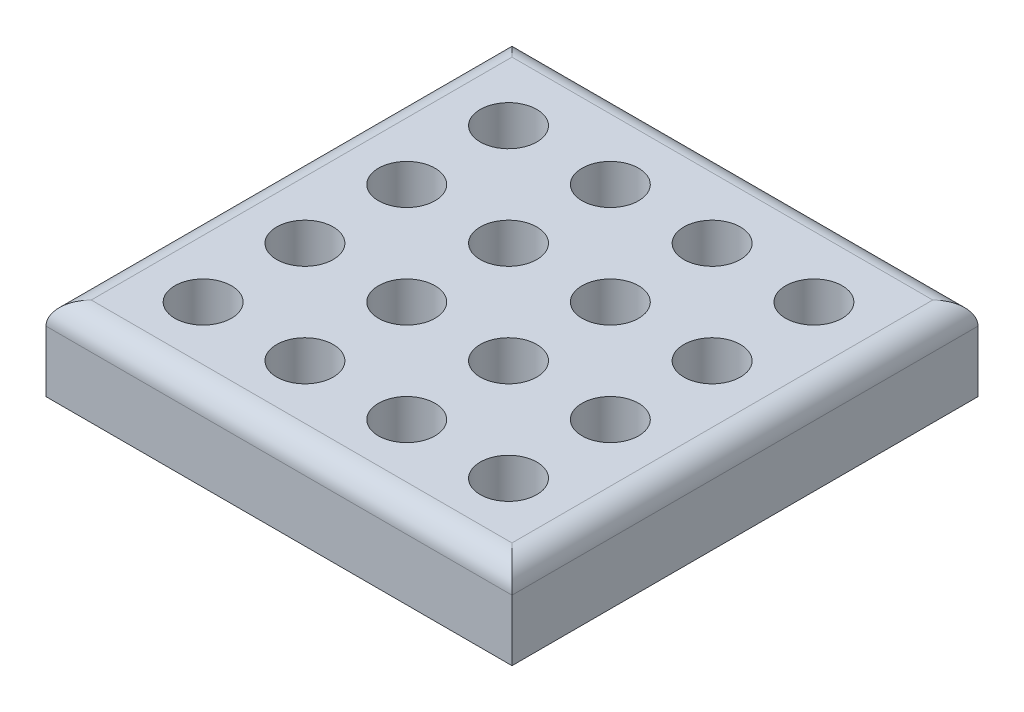
SolidWorks part; units mm, degrees
ref_plane "Front Plane" through (0, 0, 0) normal (0, 0, 1) x (1, 0, 0)
ref_plane "Top Plane" through (0, 0, 0) normal (0, 1, 0) x (1, 0, 0)
ref_plane "Right Plane" through (0, 0, 0) normal (1, 0, 0) x (0, 0, -1)
sketch "Sketch1" plane through (0, 0, 0) normal (0, 1, 0) x (1, 0, 0)
  line L1 (0, 0) -> (206, 0)
  line L2 (0, 0) -> (0, 206)
  line L3 (0, 206) -> (206, 206)
  line L4 (206, 0) -> (206, 206)
  dimension "D1" = 206
  dimension "D2" = 206
extrude "Boss-Extrude1" add sketch "Sketch1" along normal blind 37
sketch "Sketch2" plane through (0, 37, 0) normal (0, 1, 0) x (1, 0, 0)
  line L0 (35.5, 168.9652) -> (80.5, 168.9652) construction
  line L1 (206, 206) -> (0, 206) construction
  line L2 (125.5, 168.9652) -> (170.5, 168.9652) construction
  line L3 (80.5, 168.9652) -> (125.5, 168.9652) construction
  line L4 (103, 213.3576) -> (103, -10.2258) construction
  line L5 (0, 206) -> (0, 0) construction
  line L6 (206, 0) -> (206, 206) construction
  circle A3 centre (80.5, 168.9652) radius 12.5
  circle A4 centre (35.5, 168.9652) radius 12.5
  circle A5 centre (125.5, 168.9652) radius 12.5
  circle A6 centre (170.5, 168.9652) radius 12.5
  point P12 (103, -10.2257)
  point P17 (0, 0)
  dimension "D1" = 45
  dimension "D2" = 45
  dimension "D3" = 45
extrude "Cut-Extrude1" cut sketch "Sketch2" against normal blind 30
pattern_linear "LPattern1" count 4 spacing 45 along (0, 0, 1) of "Cut-Extrude1"
fillet "Fillet2" radius 10 4 edges at (103, 37, 0) (206, 37, -103) (103, 37, -206) (0, 37, -103)
